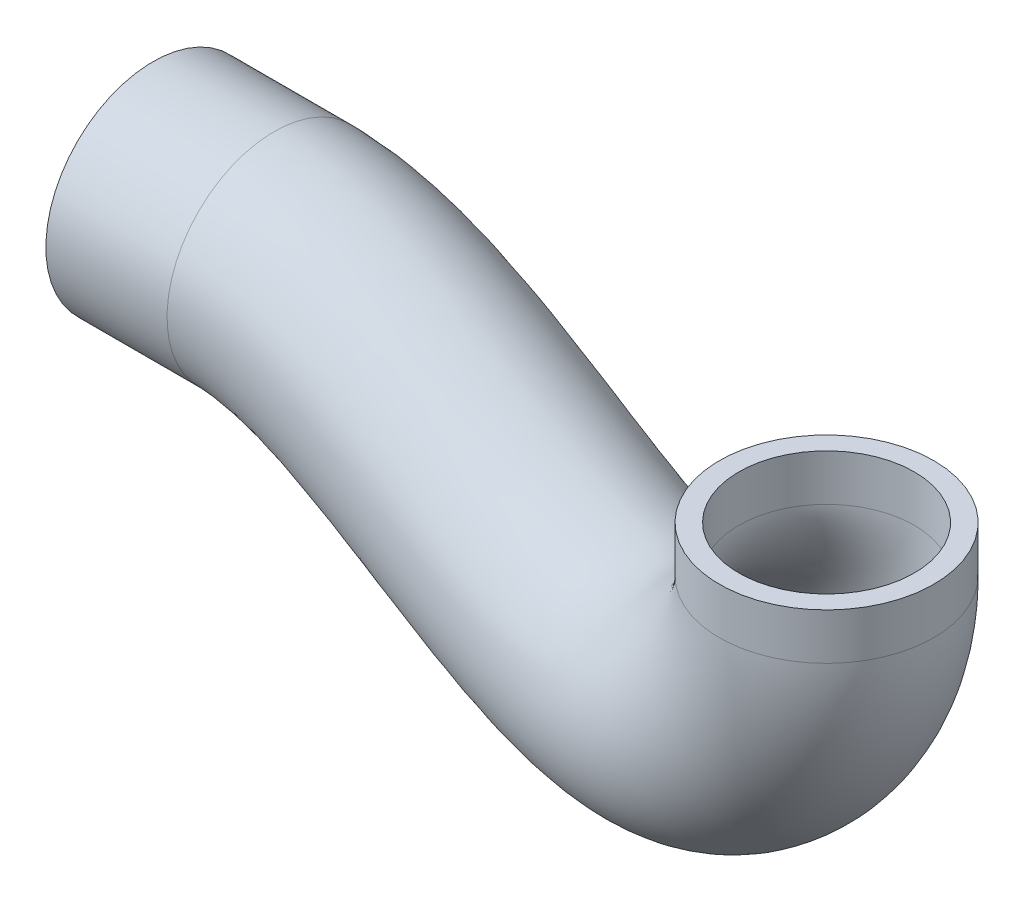
SolidWorks part; units mm, degrees
material "ABS PC"
ref_plane "Front" through (0, 0, 0) normal (0, 0, 1) x (1, 0, 0)
ref_plane "Top" through (0, 0, 0) normal (0, 1, 0) x (1, 0, 0)
ref_plane "Right" through (0, 0, 0) normal (1, 0, 0) x (0, 0, -1)
ref_axis "Axis1" through (0, 0, 55) along (0, 0, -1)
sketch3d "3DSketch1"
  line L0 (-291.0564, 81.3585, 72.9603) -> (-278.6233, 81.3585, 72.9603)
  line L1 (-211.5396, 96.3585, 83.3603) -> (-211.5396, 91.608, 83.3603)
  spline S0 degree 3 poles (-211.5396, 91.608, 83.3603) (-211.5396, 84.0944, 83.3603) (-232.9082, 56.2595, 78.8546) (-262.0703, 81.3585, 72.9603) (-278.6233, 81.3585, 72.9603) knots 0 0 0 0 0.307356 1 1 1 1
  dimension "D1" = 81.1947
ref_plane "Plane1" through (-211.5396, 96.3585, 83.3603) normal (0, -1, 0) x (-1, 0, 0)
sketch "Sketch1" plane through (-211.5396, 96.3585, 83.3603) normal (0, -1, 0) x (-1, 0, 0)
  circle A0 centre (0, 0) radius 11
  circle A1 centre (0, 0) radius 9
  dimension "D1" = 22
  dimension "D2" = 18
sweep "Sweep1" add profiles "Sketch1" path "3DSketch1"
